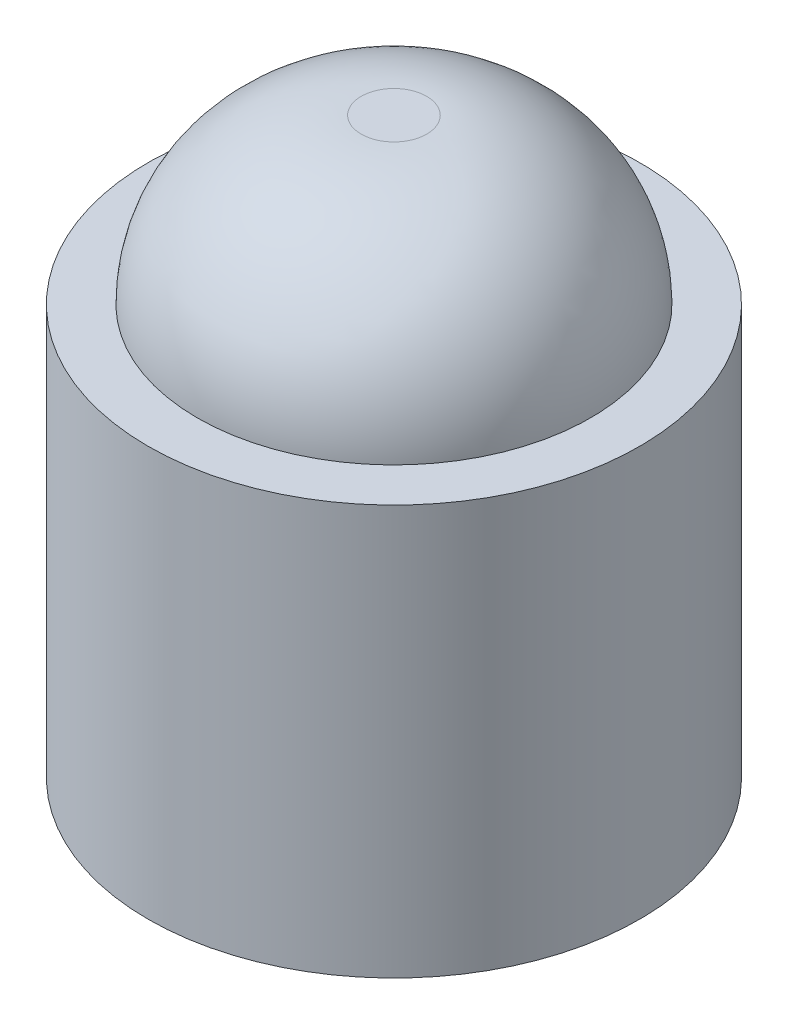
SolidWorks part; units mm, degrees
ref_plane "Front Plane" through (0, 0, 0) normal (0, 0, 1) x (1, 0, 0)
ref_plane "Top Plane" through (0, 0, 0) normal (0, 1, 0) x (1, 0, 0)
ref_plane "Right Plane" through (0, 0, 0) normal (1, 0, 0) x (0, 0, -1)
sketch "Sketch1" plane through (0, 0, 0) normal (0, 1, 0) x (1, 0, 0)
  circle A0 centre (0, 0) radius 15
  dimension "D1" = 30
extrude "Boss-Extrude1" add sketch "Sketch1" along normal blind 25
sketch "Sketch2" plane through (0, 25, 0) normal (0, 1, 0) x (1, 0, 0)
  circle A0 centre (0, 0) radius 12
extrude "Cut-Extrude1" cut sketch "Sketch2" against normal blind 10
sketch "Sketch3" plane through (0, 15, 0) normal (0, 1, 0) x (1, 0, 0)
  circle A0 centre (0, 0) radius 12
extrude "Boss-Extrude2" add sketch "Sketch3" along normal blind 20
fillet "Fillet1" radius 10 1 edges at (0, 35, 12)
